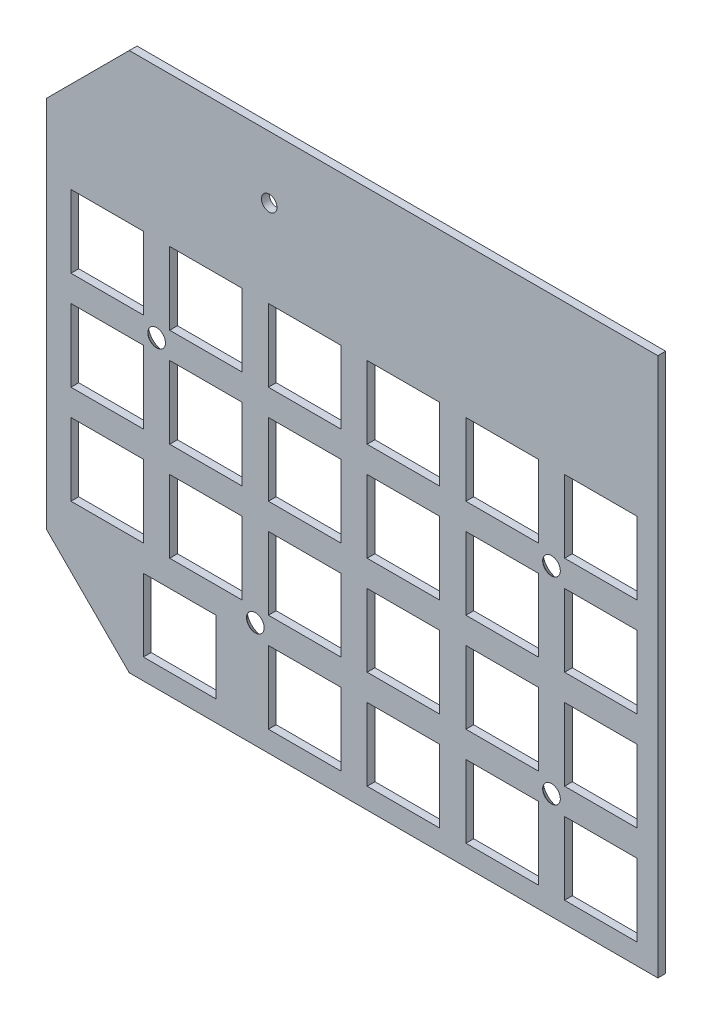
SolidWorks part; units mm, degrees
material "Alliage 1060"
ref_plane "Plan de face" through (0, 0, 0) normal (0, 0, 1) x (1, 0, 0)
ref_plane "Plan de dessus" through (0, 0, 0) normal (0, 1, 0) x (1, 0, 0)
ref_plane "Plan de droite" through (0, 0, 0) normal (1, 0, 0) x (0, 0, -1)
sketch "Esquisse1" plane through (0, 0, 0) normal (0, 0, 1) x (1, 0, 0)
  line L0 (0, -85) -> (16, -101)
  line L4 (118, 3) -> (118, -101)
  line L5 (16, 3) -> (0, -13)
  line L7 (118, 3) -> (16, 3)
  line L8 (0, -13) -> (0, -85)
  line L9 (16, -101) -> (118, -101)
  dimension "D1" = 104
  dimension "D2" = 118
  dimension "D3" = 16
  dimension "D4" = 16
  dimension "D5" = 16
  dimension "D6" = 16
extrude "Boss.-Extru.1" add sketch "Esquisse1" along normal blind 1.5
sketch "Esquisse3" plane through (0, 0, 0) normal (0, 0, -1) x (-1, 0, 0)
  line L0 (-94.95, -25.85) -> (-94.95, -39.85)
  line L1 (-114, -25.85) -> (-100, -25.85)
  line L2 (-114, -25.85) -> (-114, -39.85)
  line L3 (-114, -39.85) -> (-100, -39.85)
  line L4 (-100, -25.85) -> (-100, -39.85)
  line L5 (-107, -39.85) -> (-107, -25.85) construction
  line L6 (-114, -32.85) -> (-100, -32.85) construction
  line L7 (-94.95, -25.85) -> (-80.95, -25.85)
  line L8 (-80.95, -25.85) -> (-80.95, -39.85)
  line L9 (-94.95, -39.85) -> (-80.95, -39.85)
  line L10 (-75.9, -25.85) -> (-75.9, -39.85)
  line L11 (-75.9, -25.85) -> (-61.9, -25.85)
  line L12 (-61.9, -25.85) -> (-61.9, -39.85)
  line L13 (-75.9, -39.85) -> (-61.9, -39.85)
  line L14 (-56.85, -25.85) -> (-56.85, -39.85)
  line L15 (-56.85, -25.85) -> (-42.85, -25.85)
  line L16 (-42.85, -25.85) -> (-42.85, -39.85)
  line L17 (-56.85, -39.85) -> (-42.85, -39.85)
  line L18 (-37.8, -25.85) -> (-37.8, -39.85)
  line L19 (-37.8, -25.85) -> (-23.8, -25.85)
  line L20 (-23.8, -25.85) -> (-23.8, -39.85)
  line L21 (-37.8, -39.85) -> (-23.8, -39.85)
  line L22 (-18.75, -25.85) -> (-18.75, -39.85)
  line L23 (-18.75, -25.85) -> (-4.75, -25.85)
  line L24 (-4.75, -25.85) -> (-4.75, -39.85)
  line L25 (-18.75, -39.85) -> (-4.75, -39.85)
  line L26 (-94.95, -44.9) -> (-94.95, -58.9)
  line L27 (-94.95, -44.9) -> (-80.95, -44.9)
  line L28 (-80.95, -44.9) -> (-80.95, -58.9)
  line L29 (-94.95, -58.9) -> (-80.95, -58.9)
  line L30 (-75.9, -44.9) -> (-75.9, -58.9)
  line L31 (-75.9, -44.9) -> (-61.9, -44.9)
  line L32 (-61.9, -44.9) -> (-61.9, -58.9)
  line L33 (-75.9, -58.9) -> (-61.9, -58.9)
  line L34 (-56.85, -44.9) -> (-56.85, -58.9)
  line L35 (-56.85, -44.9) -> (-42.85, -44.9)
  line L36 (-42.85, -44.9) -> (-42.85, -58.9)
  line L37 (-56.85, -58.9) -> (-42.85, -58.9)
  line L38 (-37.8, -44.9) -> (-37.8, -58.9)
  line L39 (-37.8, -44.9) -> (-23.8, -44.9)
  line L40 (-23.8, -44.9) -> (-23.8, -58.9)
  line L41 (-37.8, -58.9) -> (-23.8, -58.9)
  line L42 (-18.75, -44.9) -> (-18.75, -58.9)
  line L43 (-18.75, -44.9) -> (-4.75, -44.9)
  line L44 (-4.75, -44.9) -> (-4.75, -58.9)
  line L45 (-18.75, -58.9) -> (-4.75, -58.9)
  line L46 (-94.95, -63.95) -> (-94.95, -77.95)
  line L47 (-94.95, -63.95) -> (-80.95, -63.95)
  line L48 (-80.95, -63.95) -> (-80.95, -77.95)
  line L49 (-94.95, -77.95) -> (-80.95, -77.95)
  line L50 (-75.9, -63.95) -> (-75.9, -77.95)
  line L51 (-75.9, -63.95) -> (-61.9, -63.95)
  line L52 (-61.9, -63.95) -> (-61.9, -77.95)
  line L53 (-75.9, -77.95) -> (-61.9, -77.95)
  line L54 (-56.85, -63.95) -> (-56.85, -77.95)
  line L55 (-56.85, -63.95) -> (-42.85, -63.95)
  line L56 (-42.85, -63.95) -> (-42.85, -77.95)
  line L57 (-56.85, -77.95) -> (-42.85, -77.95)
  line L58 (-37.8, -63.95) -> (-37.8, -77.95)
  line L59 (-37.8, -63.95) -> (-23.8, -63.95)
  line L60 (-23.8, -63.95) -> (-23.8, -77.95)
  line L61 (-37.8, -77.95) -> (-23.8, -77.95)
  line L62 (-18.75, -63.95) -> (-18.75, -77.95)
  line L63 (-18.75, -63.95) -> (-4.75, -63.95)
  line L64 (-4.75, -63.95) -> (-4.75, -77.95)
  line L65 (-18.75, -77.95) -> (-4.75, -77.95)
  line L66 (-94.95, -83) -> (-94.95, -97)
  line L67 (-94.95, -83) -> (-80.95, -83)
  line L68 (-80.95, -83) -> (-80.95, -97)
  line L69 (-94.95, -97) -> (-80.95, -97)
  line L70 (-75.9, -83) -> (-75.9, -97)
  line L71 (-75.9, -83) -> (-61.9, -83)
  line L72 (-61.9, -83) -> (-61.9, -97)
  line L73 (-75.9, -97) -> (-61.9, -97)
  line L74 (-56.85, -83) -> (-56.85, -97)
  line L75 (-56.85, -83) -> (-42.85, -83)
  line L76 (-42.85, -83) -> (-42.85, -97)
  line L77 (-56.85, -97) -> (-42.85, -97)
  line L86 (-114, -44.9) -> (-114, -58.9)
  line L87 (-114, -44.9) -> (-100, -44.9)
  line L88 (-100, -44.9) -> (-100, -58.9)
  line L89 (-114, -58.9) -> (-100, -58.9)
  line L90 (-114, -63.95) -> (-114, -77.95)
  line L91 (-114, -63.95) -> (-100, -63.95)
  line L92 (-100, -63.95) -> (-100, -77.95)
  line L93 (-114, -77.95) -> (-100, -77.95)
  line L94 (-114, -83) -> (-114, -97)
  line L95 (-114, -83) -> (-100, -83)
  line L96 (-100, -83) -> (-100, -97)
  line L97 (-114, -97) -> (-100, -97)
  line L98 (-4.75, -83) -> (-4.75, -97) [skipped]
  line L99 (-18.75, -97) -> (-4.75, -97) [skipped]
  line L100 (-18.75, -83) -> (-18.75, -97) [skipped]
  line L101 (-18.75, -83) -> (-4.75, -83) [skipped]
  line L103 (-118, -101) -> (-118, 3) construction
  line L104 (-16, -101) -> (-118, -101) construction
  line L107 (-37.8, -83) -> (-23.8, -83) [skipped]
  line L108 (-23.8, -83) -> (-23.8, -97) [skipped]
  line L109 (-37.8, -83) -> (-37.8, -97) [skipped]
  line L110 (-37.8, -97) -> (-23.8, -97) [skipped]
  line L111 (0, -13) -> (0, -85) construction
  line L112 (-32.72, -83) -> (-18.72, -83)
  line L113 (-32.72, -83) -> (-32.72, -97)
  line L114 (-32.72, -97) -> (-18.72, -97)
  line L115 (-18.72, -83) -> (-18.72, -97)
  line L116 (-25.72, -97) -> (-25.72, -83) construction
  line L117 (-32.72, -90) -> (-18.72, -90) construction
  line L122 (-118, 3) -> (-16, 3) construction
  circle A5 centre (-43, -9) radius 1.5
  point P0 (-107, -32.85)
  point P84 (-25.72, -90)
  dimension "D7" = 43
  dimension "D8" = 12
  dimension "D1" = 14
  dimension "D2" = 14
  dimension "D5" = 4
  dimension "D6" = 4
  dimension "D9" = 5.05
  dimension "D10" = 14
  dimension "D11" = 14
  dimension "D12" = 10.13
  dimension "D13" = 5.05
  dimension "D3" = 6
  dimension "D4" = 4
extrude "Enlèv. mat.-Extru.2" cut sketch "Esquisse3" against normal blind 10
sketch "Esquisse4" plane through (0, 0, 0) normal (0, 0, -1) x (-1, 0, 0)
  line L0 (-100, -39.85) -> (-94.95, -44.9) construction
  line L1 (-23.8, -39.85) -> (-18.75, -44.9) construction
  line L2 (-37.8, -77.95) -> (-42.85, -83) construction
  line L3 (-94.95, -77.95) -> (-100, -83) construction
  point P16 (-97.475, -42.375)
  point P17 (-97.475, -80.475)
  point P18 (-40.325, -80.475)
hole_wizard "Fraisage pour vis à tête fraisée M31" positions "Esquisse5" profile "Esquisse6" countersink size "M3" standard "Ansi Metric" end condition through all
sketch "Esquisse5" plane through (0, 0, 0) normal (0, 0, -1) x (-1, 0, 0)
  line L0 (-23.8, -39.85) -> (-18.75, -44.9) construction
  line L1 (-37.8, -77.95) -> (-42.85, -83) construction
  point P0 (-97.475, -42.375)
  point P3 (-97.475, -80.475)
  point P6 (-21.275, -42.375)
  point P10 (-40.325, -80.475)
sketch "Esquisse6" plane through (97.475, -42.375, 0) normal (1, 0, 0) x (0, 1, 0)
  line L0 (0, 0) -> (0, 1.5)
  line L1 (0, 1.5) -> (1.7, 1.5)
  line L2 (1.7, 1.5) -> (1.7, 1.45)
  line L3 (1.7, 1.45) -> (3.15, 0)
  line L5 (3.15, 0) -> (0, 0)
  line L6 (-1.7, 1.45) -> (-3.15, 0) construction
  line L11 (0, -6.35) -> (0, 107.95) construction
  dimension "Diamètre du perçage jusqu'au prochain" = 3.4
  dimension "Profondeur du perçage jusqu'au prochain" = 1.5
  dimension "Diamètre du fraisage entrant" = 6.3
  dimension "Angle du fraisage entrant" = 90
